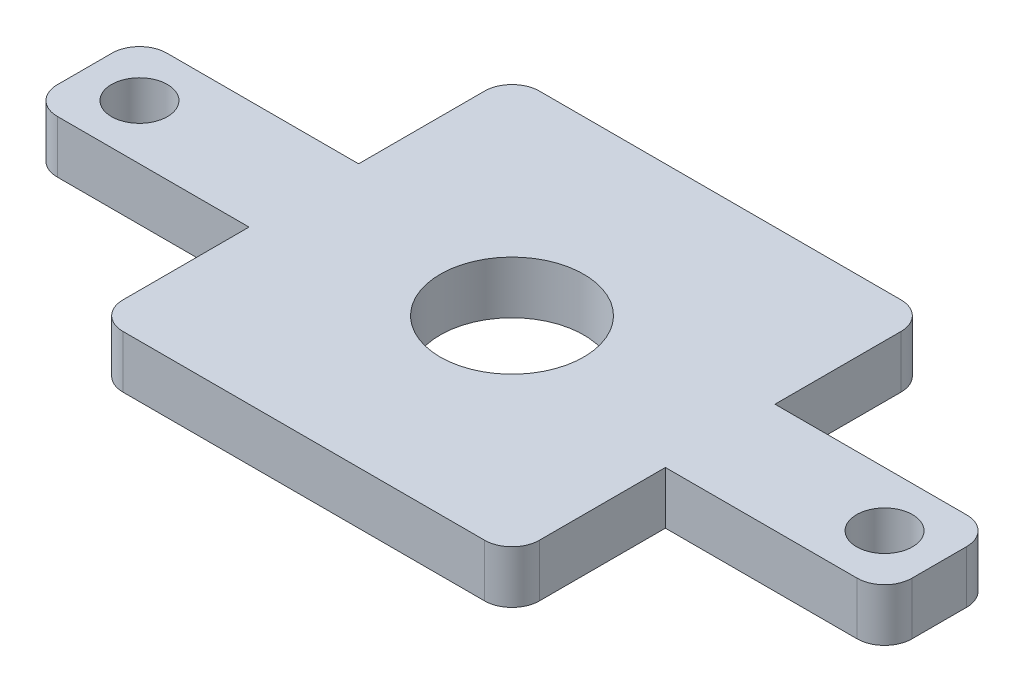
SolidWorks part; units mm, degrees
ref_plane "Front Plane" through (0, 0, 0) normal (0, 0, 1) x (1, 0, 0)
ref_plane "Top Plane" through (0, 0, 0) normal (0, 1, 0) x (1, 0, 0)
ref_plane "Right Plane" through (0, 0, 0) normal (1, 0, 0) x (0, 0, -1)
sketch "Sketch1" plane through (0, 0, 0) normal (0, 1, 0) x (1, 0, 0)
  line L0 (0, 0) -> (34, 0) construction
  line L1 (-19, -19) -> (19, -19)
  line L2 (-19, -19) -> (-19, 19)
  line L3 (-19, 19) -> (19, 19)
  line L4 (19, -19) -> (19, 19)
  line L5 (-19, -19) -> (19, 19) construction
  line L6 (-19, 19) -> (19, -19) construction
  line L7 (29, 5) -> (19, 5)
  line L8 (29, -5) -> (39, -5)
  line L9 (29, -5) -> (29, 5) construction
  line L10 (29, 5) -> (39, 5)
  line L11 (39, -5) -> (39, 5)
  line L12 (29, -5) -> (39, 5) construction
  line L13 (29, 5) -> (39, -5) construction
  line L14 (29, -5) -> (19, -5)
  line L15 (0, 19) -> (0, -19) construction
  line L16 (-29, 5) -> (-19, 5)
  line L17 (-29, -5) -> (-19, -5)
  line L18 (-29, -5) -> (-39, -5)
  line L19 (-39, -5) -> (-39, 5)
  line L20 (-29, 5) -> (-39, 5)
  circle A0 centre (0, 0) radius 18.75 construction
  circle A1 centre (34, 0) radius 2.55
  circle A2 centre (-34, 0) radius 2.55
  circle A3 centre (0, 0) radius 6.55
  dimension "D1" = 37.5
  dimension "D4" = 5.1
  dimension "D6" = 13.1
  dimension "D2" = 38
  dimension "D3" = 34
  dimension "D5" = 10
extrude "Boss-Extrude1" add sketch "Sketch1" along normal blind 4.8 contours L1 L4 L3 L2 A3 | L16 L20 L19 L18 L17 L2 A2 | L14 L8 L11 L10 L7 L4 A1 region at (-18.4626, 0, 12) region at (-28.4312, 0, 0) region at (28.4312, 0, 0)
fillet "Fillet1" radius 2.5 8 edges at (39, 2.4, -5) (39, 2.4, 5) (-39, 2.4, -5) (-39, 2.4, 5) (19, 2.4, 19) (-19, 2.4, 19) (-19, 2.4, -19) (19, 2.4, -19)
